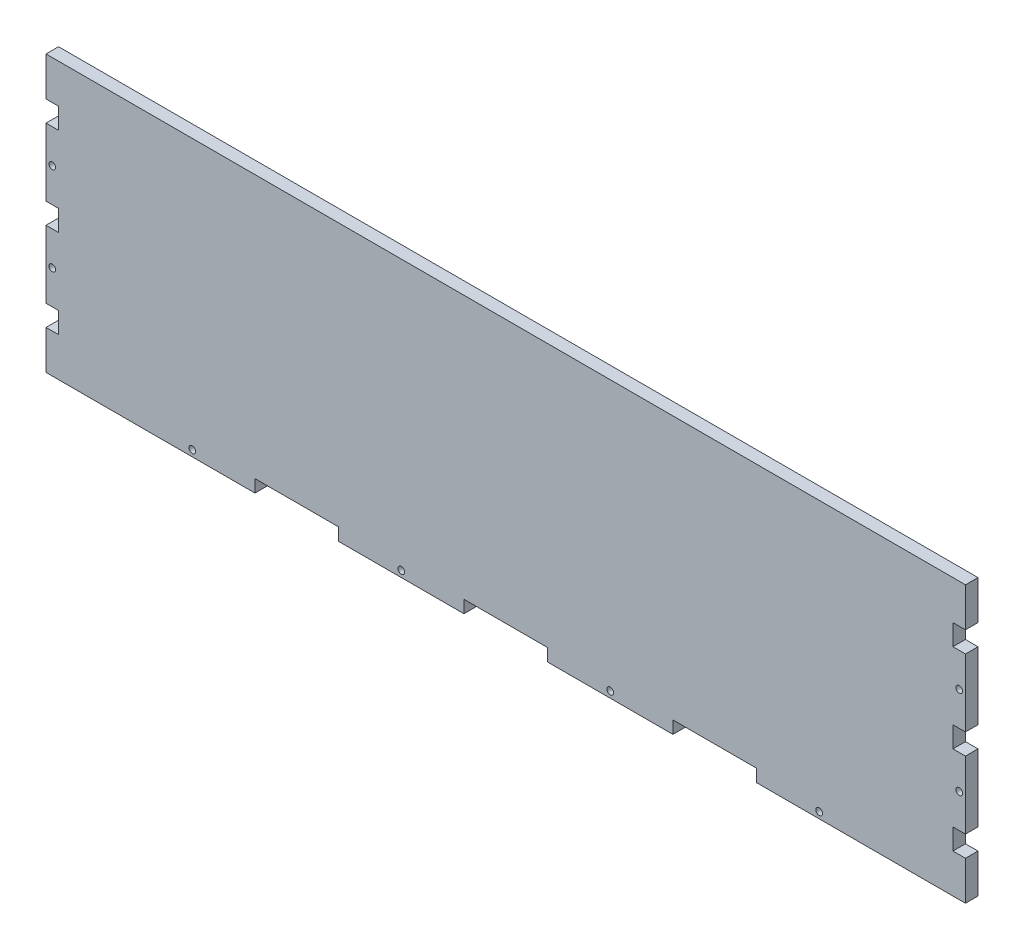
SolidWorks part; units mm, degrees
ref_plane "Front Plane" through (0, 0, 0) normal (0, 0, 1) x (1, 0, 0)
ref_plane "Top Plane" through (0, 0, 0) normal (0, 1, 0) x (1, 0, 0)
ref_plane "Right Plane" through (0, 0, 0) normal (1, 0, 0) x (0, 0, -1)
sketch "Sketch1" plane through (0, 0, 0) normal (0, 0, 1) x (1, 0, 0)
  line L1 (-220, -66) -> (220, -66)
  line L2 (-220, -66) -> (-220, 66)
  line L3 (-220, 66) -> (220, 66)
  line L4 (220, -66) -> (220, 66)
  line L5 (-220, -66) -> (220, 66) construction
  line L6 (-220, 66) -> (220, -66) construction
  point P0 (0, 0)
  dimension "D1" = 440
  dimension "D2" = 132
extrude "Boss-Extrude1" add sketch "Sketch1" along normal blind 6
sketch "Sketch2" plane through (0, 0, 0) normal (0, 0, -1) x (-1, 0, 0)
  line L0 (220, 47.3321) -> (220, 37.3321) construction
  line L1 (220, 37.3321) -> (214, 37.3321) construction
  line L2 (214, 37.3321) -> (214, 47.3321) construction
  line L3 (214, 47.3321) -> (220, 47.3321) construction
  line L12 (220, -37.3321) -> (220, -47.3321) construction
  line L13 (220, -47.3321) -> (214, -47.3321) construction
  line L14 (214, -47.3321) -> (214, -37.3321) construction
  line L15 (214, -37.3321) -> (220, -37.3321) construction
  line L16 (220, 47.3321) -> (220, 37.3321)
  line L17 (220, 37.3321) -> (214, 37.3321)
  line L18 (214, 37.3321) -> (214, 47.3321)
  line L19 (214, 47.3321) -> (220, 47.3321)
  line L20 (220, -37.3321) -> (220, -47.3321)
  line L21 (220, -47.3321) -> (214, -47.3321)
  line L22 (214, -47.3321) -> (214, -37.3321)
  line L23 (214, -37.3321) -> (220, -37.3321)
  line L24 (-214, -37.3321) -> (-214, -47.3321) construction
  line L25 (-214, -47.3321) -> (-220, -47.3321) construction
  line L26 (-220, -47.3321) -> (-220, -37.3321) construction
  line L27 (-220, -37.3321) -> (-214, -37.3321) construction
  line L28 (-214, 47.3321) -> (-214, 37.3321) construction
  line L29 (-214, 37.3321) -> (-220, 37.3321) construction
  line L30 (-220, 37.3321) -> (-220, 47.3321) construction
  line L31 (-220, 47.3321) -> (-214, 47.3321) construction
  line L32 (-214, -37.3321) -> (-214, -47.3321)
  line L33 (-214, -47.3321) -> (-220, -47.3321)
  line L34 (-220, -47.3321) -> (-220, -37.3321)
  line L35 (-220, -37.3321) -> (-214, -37.3321)
  line L36 (-214, 47.3321) -> (-214, 37.3321)
  line L37 (-214, 37.3321) -> (-220, 37.3321)
  line L38 (-220, 37.3321) -> (-220, 47.3321)
  line L39 (-220, 47.3321) -> (-214, 47.3321)
  line L44 (220, -5) -> (220, 5)
  line L45 (214, -5) -> (220, -5)
  line L46 (214, 5) -> (214, -5)
  line L47 (220, 5) -> (214, 5)
  line L48 (220, -5) -> (220, 5)
  line L49 (214, -5) -> (220, -5)
  line L50 (214, 5) -> (214, -5)
  line L51 (220, 5) -> (214, 5)
  line L52 (-214, -5) -> (-214, 5)
  line L53 (-220, -5) -> (-214, -5)
  line L54 (-220, 5) -> (-220, -5)
  line L55 (-214, 5) -> (-220, 5)
  line L56 (-214, -5) -> (-214, 5)
  line L57 (-220, -5) -> (-214, -5)
  line L58 (-220, 5) -> (-220, -5)
  line L59 (-214, 5) -> (-220, 5)
  circle A0 centre (217, 21.1661) radius 1.6 construction
  circle A1 centre (217, -21.1661) radius 1.6 construction
  circle A2 centre (-217, 21.1661) radius 1.6 construction
  circle A3 centre (-217, -21.1661) radius 1.6 construction
  circle A4 centre (217, 21.1661) radius 1.6
  circle A5 centre (217, -21.1661) radius 1.6
  circle A6 centre (-217, 21.1661) radius 1.6
  circle A7 centre (-217, -21.1661) radius 1.6
  dimension "D2" = 0
  dimension "D3" = 0
extrude "Cut-Extrude1" cut sketch "Sketch2" against normal up to next
sketch "Sketch3" plane through (0, 0, 0) normal (0, 0, -1) x (-1, 0, 0)
  circle A0 centre (-150, -63) radius 1.6 construction
  circle A1 centre (-50, -63) radius 1.6 construction
  circle A2 centre (50, -63) radius 1.6 construction
  circle A3 centre (150, -63) radius 1.6 construction
  circle A4 centre (-150, -63) radius 1.6
  circle A5 centre (-50, -63) radius 1.6
  circle A6 centre (50, -63) radius 1.6
  circle A7 centre (150, -63) radius 1.6
extrude "Cut-Extrude2" cut sketch "Sketch3" against normal up to next
sketch "Sketch4" plane through (0, 0, 0) normal (0, 0, -1) x (-1, 0, 0)
  line L0 (80, -66) -> (120, -66) construction
  line L1 (120, -66) -> (120, -60) construction
  line L2 (120, -60) -> (80, -60) construction
  line L3 (80, -60) -> (80, -66) construction
  line L4 (-20, -66) -> (20, -66) construction
  line L5 (20, -66) -> (20, -60) construction
  line L6 (20, -60) -> (-20, -60) construction
  line L7 (-20, -60) -> (-20, -66) construction
  line L8 (-120, -66) -> (-80, -66) construction
  line L9 (-80, -66) -> (-80, -60) construction
  line L10 (-80, -60) -> (-120, -60) construction
  line L11 (-120, -60) -> (-120, -66) construction
  line L12 (80, -66) -> (120, -66)
  line L13 (120, -66) -> (120, -60)
  line L14 (120, -60) -> (80, -60)
  line L15 (80, -60) -> (80, -66)
  line L16 (-20, -66) -> (20, -66)
  line L17 (20, -66) -> (20, -60)
  line L18 (20, -60) -> (-20, -60)
  line L19 (-20, -60) -> (-20, -66)
  line L20 (-120, -66) -> (-80, -66)
  line L21 (-80, -66) -> (-80, -60)
  line L22 (-80, -60) -> (-120, -60)
  line L23 (-120, -60) -> (-120, -66)
extrude "Cut-Extrude3" cut sketch "Sketch4" against normal up to next
